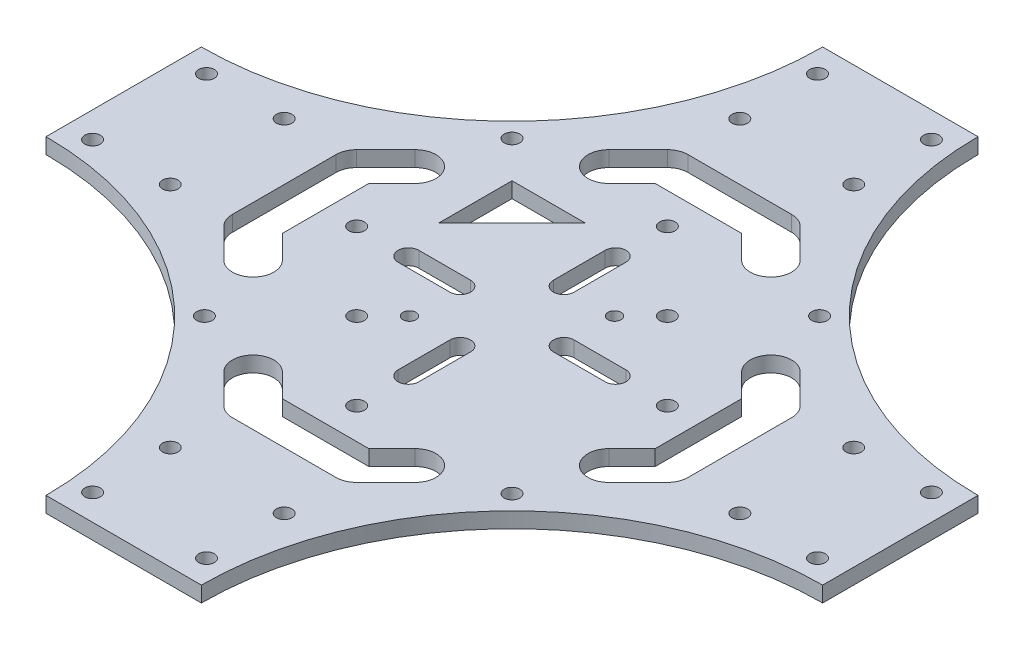
SolidWorks part; units mm, degrees
material "Hexcel AS4C (3000 丝)"
ref_plane "前视基准面" through (0, 0, 0) normal (0, 0, 1) x (1, 0, 0)
ref_plane "上视基准面" through (0, 0, 0) normal (0, 1, 0) x (1, 0, 0)
ref_plane "右视基准面" through (0, 0, 0) normal (1, 0, 0) x (0, 0, -1)
sketch "草图1" plane through (0, 0, 0) normal (0, 1, 0) x (1, 0, 0)
  line L0 (0, 0) -> (0, 75)
  line L1 (0, 0) -> (75, 0)
  line L2 (0, 0) -> (0, -75)
  line L3 (0, 0) -> (-75, 0)
  line L4 (0, 75) -> (15, 75)
  line L5 (0, 75) -> (-15, 75)
  line L6 (75, 0) -> (75, 15)
  line L7 (75, 0) -> (75, -15)
  line L8 (0, -75) -> (15, -75)
  line L9 (0, -75) -> (-15, -75)
  line L10 (-75, 0) -> (-75, -15)
  line L11 (-75, 0) -> (-75, 15)
  line L12 (75, 0) -> (70, 0)
  arc A0 (-75, 15) -> (-15, 75) centre (-75, 75) ccw
  arc A1 (15, 75) -> (75, 15) centre (75, 75) ccw
  arc A2 (75, -15) -> (15, -75) centre (75, -75) ccw
  arc A3 (-15, -75) -> (-75, -15) centre (-75, -75) ccw
  circle A4 centre (-11, 70) radius 1.25
  circle A5 centre (11, 70) radius 1.25
  circle A6 centre (70, -11) radius 1.25
  circle A7 centre (70, 11) radius 1.25
  circle A8 centre (-11, -70) radius 1.25
  circle A9 centre (11, -70) radius 1.25
  circle A10 centre (-70, 11) radius 1.25
  circle A11 centre (-70, -11) radius 1.25
  point P9 (0, 0)
  point P21 (0, 0)
  point P32 (0, 0)
  point P35 (0, 0)
  point P44 (0, 0)
  dimension "D1" = 4
extrude "凸台-拉伸1" add sketch "草图1" along normal blind 3 contours A2 L7 L1 L2 L8 A9 A6 | A3 L9 L2 L3 L10 A11 A8 | A0 L11 L3 L0 L5 A4 A10 | A1 L4 L0 L1 L6 A7 A5 region at (-25.2829, 0, -25.2829) region at (25.2829, 0, -25.2829) region at (25.2829, 0, 25.2829) region at (-25.2829, 0, 25.2829)
sketch "草图2" plane through (0, 0, 0) normal (0, -1, 0) x (1, 0, 0)
  line L0 (0, 0) -> (-32.5736, -32.5736)
  line L1 (0, 0) -> (32.5736, -32.5736)
  line L2 (-31.4663, 0.3536) -> (-0.3536, 31.4663)
  line L3 (31.4663, -0.3536) -> (-0.3536, 31.4663)
  line L4 (0.3536, -31.4663) -> (31.4663, -0.3536)
  line L5 (0.3536, -31.4663) -> (-31.4663, 0.3536)
  arc A0 (-15, -75) -> (-75, -15) centre (-75, -75) ccw construction
  circle A2 centre (0.3536, -31.4663) radius 1.5
  circle A3 centre (31.4663, -0.3536) radius 1.5
  circle A4 centre (-0.3536, 31.4663) radius 1.5
  circle A5 centre (-31.4663, 0.3536) radius 1.5
  point P12 (-15.5563, -15.5563)
  point P16 (-15.9099, 15.9099)
  point P17 (15.9099, -15.9099)
extrude "切除-拉伸1" cut sketch "草图2" against normal blind 3 contours A3 | A2 | A5 | A4
sketch "草图3" plane through (0, 3, 0) normal (0, 1, 0) x (1, 0, 0)
  line L0 (0.3536, 31.4663) -> (-31.4663, -0.3536)
  line L1 (-15.5563, 15.5563) -> (-22.6274, 22.6274)
  line L2 (-15.5563, 15.5563) -> (-12.0208, 19.0919)
  line L3 (-15.5563, 15.5563) -> (-19.0919, 12.0208)
  line L4 (-19.0919, 12.0208) -> (-22.6274, 22.6274)
  line L5 (-12.0208, 19.0919) -> (-22.6274, 22.6274)
extrude "切除-拉伸2" cut sketch "草图3" against normal blind 3 contours L0 L5 L1 | L4 L0 L1 region at (-16.7349, 3, -19.0919) region at (-19.0919, 3, -16.7349)
sketch "草图4" plane through (0, 3, 0) normal (0, 1, 0) x (1, 0, 0)
  line L0 (31.4663, 0.3536) -> (-0.3536, -31.4663)
  line L1 (0, 0) -> (21.2132, -21.2132)
  line L2 (28.2843, -14.1421) -> (14.1421, -28.2843)
  line L3 (14.1421, -28.2843) -> (28.2843, -14.1421) construction
  line L4 (8.4817, -22.6239) -> (22.6239, -8.4817)
  line L5 (19.8025, -33.9447) -> (33.9447, -19.8025)
  arc A0 (8.4817, -22.6239) -> (19.8025, -33.9447) centre (14.1421, -28.2843) ccw
  arc A1 (33.9447, -19.8025) -> (22.6239, -8.4817) centre (28.2843, -14.1421) ccw
  point P9 (21.2132, -21.2132)
extrude "切除-拉伸3" cut sketch "草图4" against normal blind 3 contours L5 A1 L0 A0 region at (21.2143, 3, 21.2143)
sketch "草图5" plane through (0, 3, 0) normal (0, 1, 0) x (1, 0, 0)
  line L0 (-12.0208, 19.0919) -> (-8.4853, 22.6274)
  line L1 (-8.4853, 22.6274) -> (-22.6274, 22.6274)
  line L2 (-19.0919, 12.0208) -> (-22.6274, 8.4853)
  line L3 (-22.6274, 8.4853) -> (-22.6274, 22.6274)
  line L4 (-12.0208, 19.0919) -> (-22.6274, 22.6274)
  line M28 (-19.0919, 12.0208) -> (-22.6274, 22.6274)
extrude "切除-拉伸4" cut sketch "草图5" against normal blind 10 contours L3 L2 M28 | L4 L0 L1 region at (-21.4489, 3, -14.3778)
sketch "草图6" plane through (0, 3, 0) normal (0, 1, 0) x (1, 0, 0)
  line L0 (0, 0) -> (-28.2843, -28.2843)
  line L1 (-28.2843, -28.2843) -> (-35.3553, -21.2132)
  line L2 (0, 0) -> (-22.6274, 22.6274)
  circle A0 centre (-35.3553, -21.2132) radius 1.5
  circle A1 centre (-21.2132, -35.3553) radius 1.5
  circle A2 centre (35.3553, 21.2132) radius 1.5
  circle A3 centre (21.2132, 35.3553) radius 1.5
extrude "切除-拉伸5" cut sketch "草图6" against normal blind 10 contours A1 | A0 | A2 | A3
sketch "草图7" plane through (0, 3, 0) normal (0, 1, 0) x (1, 0, 0)
  circle A0 centre (-29.6985, 29.6985) radius 1.5
  circle A1 centre (29.6985, 29.6985) radius 1.5
  circle A2 centre (29.6985, -29.6985) radius 1.5
  circle A3 centre (-29.6985, -29.6985) radius 1.5
  point P11 (0, 0)
  dimension "D1" = 4
extrude "切除-拉伸8" cut sketch "草图7" against normal blind 10
sketch "草图8" plane through (0, 3, 0) normal (0, 1, 0) x (1, 0, 0)
  circle A0 centre (-11, 55) radius 1.5
  circle A1 centre (11, 55) radius 1.5
  circle A2 centre (55, 11) radius 1.5
  circle A3 centre (55, -11) radius 1.5
  circle A4 centre (11, -55) radius 1.5
  circle A5 centre (-11, -55) radius 1.5
  circle A6 centre (-55, -11) radius 1.5
  circle A7 centre (-55, 11) radius 1.5
  point P21 (0, 0)
  dimension "D1" = 4
extrude "切除-拉伸9" cut sketch "草图8" against normal blind 10
sketch "草图9" plane through (0, 3, 0) normal (0, 1, 0) x (1, 0, 0)
  circle A0 centre (0, 0) radius 15
extrude "切除-拉伸10" cut sketch "草图9" against normal blind 10
sketch "草图11" plane through (0, 3, 0) normal (0, 1, 0) x (1, 0, 0)
  circle A0 centre (-35.3553, -21.2132) radius 1.5
  circle A2 centre (35.3553, 21.2132) radius 1.5
  circle A3 centre (21.2132, 35.3553) radius 1.5
  circle A4 centre (0.3536, 31.4663) radius 1.5
  circle A5 centre (31.4663, 0.3536) radius 1.5
  circle A6 centre (-0.3536, -31.4663) radius 1.5
  circle A7 centre (-31.4663, -0.3536) radius 1.5
  circle A8 centre (-21.2132, -35.3553) radius 1.5
extrude "凸台-拉伸3" add sketch "草图11" against normal blind 3
sketch "草图12" plane through (0, 3, 0) normal (0, 1, 0) x (1, 0, 0)
  line L0 (0, 0) -> (-40, 0)
  line L1 (-40, 0) -> (-40, 10)
  line L2 (-40, 0) -> (-40, -10)
  line L3 (-40, -10) -> (-40, 10) construction
  line L4 (-44, -10) -> (-44, 10)
  line L5 (-36, -10) -> (-36, 10)
  line L6 (-10, 40) -> (10, 40) construction
  line L7 (-10, 44) -> (10, 44)
  line L8 (-10, 36) -> (10, 36)
  line L9 (40, 10) -> (40, -10) construction
  line L10 (44, 10) -> (44, -10)
  line L11 (36, 10) -> (36, -10)
  line L12 (10, -40) -> (-10, -40) construction
  line L13 (10, -44) -> (-10, -44)
  line L14 (10, -36) -> (-10, -36)
  arc A0 (-44, -10) -> (-36, -10) centre (-40, -10) ccw
  arc A1 (-36, 10) -> (-44, 10) centre (-40, 10) ccw
  arc A2 (-10, 44) -> (-10, 36) centre (-10, 40) ccw
  arc A3 (10, 36) -> (10, 44) centre (10, 40) ccw
  arc A4 (44, 10) -> (36, 10) centre (40, 10) ccw
  arc A5 (36, -10) -> (44, -10) centre (40, -10) ccw
  arc A6 (10, -44) -> (10, -36) centre (10, -40) ccw
  arc A7 (-10, -36) -> (-10, -44) centre (-10, -40) ccw
  point P3 (-40, 0)
  point P13 (0, 40)
  point P20 (40, 0)
  point P27 (0, -40)
  point P34 (0, 0)
  dimension "D1" = 4
extrude "切除-拉伸12" cut sketch "草图12" against normal blind 3 contours L5 A1 L4 A0 | L8 A3 L7 A2 | L11 A5 L10 A4 | L14 A7 L13 A6 region at (-43.7088, 3, 0) region at (0, 3, -40) region at (40, 3, 0) region at (0, 3, 40)
sketch "草图14" plane through (0, 3, 0) normal (0, 1, 0) x (1, 0, 0)
  line L0 (22.8277, -8.285) -> (8.285, -22.8277) construction
  line L1 (19.8025, -33.9447) -> (33.9447, -19.8025) construction
  line L2 (8.285, -22.8277) -> (22.8277, -8.285)
  line L3 (22.8277, -8.285) -> (19.8025, -33.9447)
  line L4 (19.8025, -33.9447) -> (33.9447, -19.8025)
  arc A0 (8.285, -22.8277) -> (19.8025, -33.9447) centre (14.1421, -28.2843) ccw
  arc A1 (8.285, -22.8277) -> (19.8025, -33.9447) centre (14.1421, -28.2843) ccw construction
  arc A2 (33.9447, -19.8025) -> (22.8277, -8.285) centre (28.2843, -14.1421) ccw construction
  arc A3 (22.8277, -8.285) -> (32.1857, -7.1522) centre (28.2843, -14.1421) ccw
  circle A4 centre (28.2843, -14.1421) radius 8.005
extrude "凸台-拉伸4" add sketch "草图14" against normal blind 3 contours A3 A4 L3 | L2 A3 L3 | A3 L2 A0 L3 | A3 L3 L4 region at (14.6624, 3, 25.7239) region at (21.4582, 3, 13.3381) region at (24.21, 3, 25.4431) region at (28.7736, 3, 14.1998)
sketch "草图15" plane through (0, 3, 0) normal (0, 1, 0) x (1, 0, 0)
  circle A0 centre (0, 0) radius 15
extrude "凸台-拉伸5" add sketch "草图15" against normal blind 3
sketch "草图17" plane through (0, 3, 0) normal (0, 1, 0) x (1, 0, 0)
  line L0 (0, 0) -> (0, -20)
  line L1 (0, -20) -> (0, -10) construction
  line L2 (-2, -20) -> (-2, -10)
  line L3 (2, -20) -> (2, -10)
  line L4 (-20, 0) -> (-10, 0) construction
  line L5 (-20, 2) -> (-10, 2)
  line L6 (-20, -2) -> (-10, -2)
  line L7 (0, 20) -> (0, 10) construction
  line L8 (2, 20) -> (2, 10)
  line L9 (-2, 20) -> (-2, 10)
  line L10 (20, 0) -> (10, 0) construction
  line L11 (20, -2) -> (10, -2)
  line L12 (20, 2) -> (10, 2)
  arc A0 (-2, -20) -> (2, -20) centre (0, -20) ccw
  arc A1 (2, -10) -> (-2, -10) centre (0, -10) ccw
  arc A2 (-20, 2) -> (-20, -2) centre (-20, 0) ccw
  arc A3 (-10, -2) -> (-10, 2) centre (-10, 0) ccw
  arc A4 (2, 20) -> (-2, 20) centre (0, 20) ccw
  arc A5 (-2, 10) -> (2, 10) centre (0, 10) ccw
  arc A6 (20, -2) -> (20, 2) centre (20, 0) ccw
  arc A7 (10, 2) -> (10, -2) centre (10, 0) ccw
  point P3 (0, -15)
  point P13 (-15, 0)
  point P20 (0, 15)
  point P27 (15, 0)
  point P33 (0, 0)
  dimension "D1" = 4
extrude "切除-拉伸13" cut sketch "草图17" against normal blind 3 contours L8 A5 L9 A4 | L12 A7 L11 A6 | L3 A1 L2 A0 | L5 A3 L6 A2
sketch "草图18" plane through (0, 3, 0) normal (0, 1, 0) x (1, 0, 0)
  line L0 (0, 0) -> (-32.5736, 32.5736)
  line L1 (-32.5736, 32.5736) -> (-46.7157, 46.7157)
  line L2 (-50.2513, 50.2513) -> (-61.9773, 38.5252)
  line L3 (-46.7157, 46.7157) -> (-50.2513, 50.2513)
  line L4 (-61.9773, 38.5252) -> (-38.5252, 61.9773)
  line L5 (-38.5252, 61.9773) -> (-22.5002, 45.9523)
  line L6 (-61.9773, 38.5252) -> (-45.9523, 22.5002)
  arc A0 (-75, 15) -> (-15, 75) centre (-75, 75) ccw construction
  circle A1 centre (-67.9289, 67.9289) radius 30
  circle A2 centre (-75, 75) radius 60
extrude "凸台-拉伸7" add sketch "草图18" against normal blind 3 contours L4 A1 L2 | L2 A1 L3 | L3 A1 L4 | L6 A2 L1 A1 | L1 A2 L5 A1 region at (-46.4984, 3, -34.5306) region at (-34.5306, 3, -46.4984) region at (-53.277, 3, -44.3758) region at (-44.3758, 3, -53.277) region at (-68.7208, 3, -68.7208)
sketch "草图19" plane through (0, 3, 0) normal (0, 1, 0) x (1, 0, 0)
  line L0 (-61.9773, 38.5252) -> (-38.5252, 61.9773)
  line L1 (-50.2513, 50.2513) -> (-36.1091, 36.1091)
  line L2 (-36.1091, 36.1091) -> (-43.1802, 29.0381)
  line L3 (-36.1091, 36.1091) -> (-29.0381, 43.1802)
  line L4 (-29.0381, 43.1802) -> (-37.1408, 51.2829)
  line L5 (-37.1408, 51.2829) -> (-51.2829, 37.1408)
  line L6 (-51.2829, 37.1408) -> (-43.1802, 29.0381)
  circle A1 centre (-67.9289, 67.9289) radius 35
  circle A2 centre (-67.9289, 67.9289) radius 45
extrude "切除-拉伸14" cut sketch "草图19" against normal blind 3 contours L1 A2 L4 A1 | L6 A2 L1 A1 region at (-36.3949, 3, -43.5045) region at (-43.5045, 3, -36.3949)
sketch "草图21" plane through (0, 3, 0) normal (0, 1, 0) x (1, 0, 0)
  line L0 (-61.9773, 38.5252) -> (-38.5252, 61.9773)
  line L1 (-67.9289, 67.9289) -> (-53.7868, 53.7868)
  line L2 (-82.0711, 82.0711) -> (-75, 75)
  line L3 (-67.9289, 67.9289) -> (-82.0711, 82.0711)
  line L4 (-53.7868, 53.7868) -> (-60.8579, 60.8579)
  line L5 (-82.0711, 82.0711) -> (-75, 75) construction
  line L6 (-81.1872, 82.955) -> (-74.1161, 75.8839)
  line L7 (-82.955, 81.1872) -> (-75.8839, 74.1161)
  line L8 (-60.8579, 60.8579) -> (-53.7868, 53.7868) construction
  line L9 (-59.974, 61.7417) -> (-52.9029, 54.6707)
  line L10 (-61.7417, 59.974) -> (-54.6707, 52.9029)
  arc A0 (-81.1872, 82.955) -> (-82.955, 81.1872) centre (-82.0711, 82.0711) ccw
  arc A1 (-75.8839, 74.1161) -> (-74.1161, 75.8839) centre (-75, 75) ccw
  arc A2 (-59.974, 61.7417) -> (-61.7417, 59.974) centre (-60.8579, 60.8579) ccw
  arc A3 (-54.6707, 52.9029) -> (-52.9029, 54.6707) centre (-53.7868, 53.7868) ccw
  point P2 (-78.5355, 78.5355)
  point P15 (-57.3223, 57.3223)
extrude "切除-拉伸15" cut sketch "草图21" against normal blind 3 contours A1 L6 A0 L7 | A3 L9 A2 L10 region at (-75, 3, -73.8854)
pattern_circular "阵列(圆周)1" count 8 over 360 about axis through (-67.9289, 3, -67.9289) along (0, 1, 0) of "切除-拉伸15"
sketch "草图22" plane through (0, 3, 0) normal (0, 1, 0) x (1, 0, 0)
  line L0 (0, 0) -> (9.8995, 9.8995)
  line L1 (0, 0) -> (-9.8995, -9.8995)
  circle A0 centre (9.8995, 9.8995) radius 1.25
  circle A1 centre (-9.8995, -9.8995) radius 1.25
extrude "切除-拉伸17" cut sketch "草图22" against normal blind 3 contours A0 | A1
sketch "草图23" plane through (0, 3, 0) normal (0, 1, 0) x (1, 0, 0)
  circle A0 centre (0, 30) radius 1.5
  circle A1 centre (30, 0) radius 1.5
  circle A2 centre (0, -30) radius 1.5
  circle A3 centre (-30, 0) radius 1.5
  point P13 (0, 0)
  dimension "D1" = 4
extrude "切除-拉伸18" cut sketch "草图23" against normal blind 10
sketch "草图24" plane through (0, 3, 0) normal (0, 1, 0) x (1, 0, 0)
  circle A0 centre (-15, -15) radius 1.5
  circle A1 centre (15, 15) radius 1.5
extrude "切除-拉伸19" cut sketch "草图24" against normal blind 10
sketch "草图25" plane through (0, 3, 0) normal (0, 1, 0) x (1, 0, 0)
  circle A0 centre (-75, 75) radius 60
extrude "切除-拉伸20" cut sketch "草图25" against normal blind 10
sketch "草图26" plane through (0, 3, 0) normal (0, 1, 0) x (1, 0, 0)
  line L0 (-15, 75) -> (-75, 15)
  circle A0 centre (-75, 75) radius 60
extrude "凸台-拉伸8" add sketch "草图26" against normal blind 3 contours L0 A0 region at (-39.9612, 3, -39.9612)
sketch "草图27" plane through (0, 0, 0) normal (0, -1, 0) x (1, 0, 0)
  line L0 (-45, -45) -> (-23.5998, -66.4002)
  line L1 (-15, -75) -> (-75, -15) construction
  line L2 (-23.5998, -66.4002) -> (-66.0262, -23.9738)
  line L3 (-15, -75) -> (-22.0711, -82.0711)
  line L4 (-22.0711, -82.0711) -> (-75, -15)
  line L5 (-75, -15) -> (-82.0711, -22.0711)
  line L6 (-82.0711, -22.0711) -> (-22.0711, -82.0711)
  line L7 (75, 15) -> (15, 75)
  line L8 (15, 75) -> (22.0711, 82.0711)
  line L9 (75, 15) -> (82.0711, 22.0711)
  line L10 (82.0711, 22.0711) -> (22.0711, 82.0711)
  line L11 (-15, -75) -> (-75, -15)
  line L12 (-22.0711, -82.0711) -> (-29.1421, -89.1421)
  line L13 (-29.1421, -89.1421) -> (-82.0711, -22.0711)
  line L14 (-82.0711, -22.0711) -> (-89.1421, -29.1421)
  line L15 (-89.1421, -29.1421) -> (-29.1421, -89.1421)
  circle A0 centre (75, 75) radius 60
extrude "凸台-拉伸10" add sketch "草图27" against normal blind 3 contours L14 L15 L13 | L13 L12 L6 | L5 L6 L4 | L3 L11 L0 L2 L4 region at (-37.357, 0, -57.357) region at (-59.714, 0, -39.714) region at (-44.4281, 0, -64.4281) region at (-66.7851, 0, -46.7851)
sketch "草图28" plane through (0, 0, 0) normal (0, -1, 0) x (1, 0, 0)
  line L0 (-59.1421, -59.1421) -> (-52.0711, -52.0711)
  line L1 (-89.1421, -29.1421) -> (-29.1421, -89.1421) construction
  line L2 (-52.0711, -52.0711) -> (-25.9081, -78.234)
  line L3 (-52.0711, -52.0711) -> (-78.234, -25.9081)
  line L4 (11, -70) -> (8.198, -68.4493)
  circle A1 centre (11, -70) radius 1.5
  circle A2 centre (-11, -70) radius 1.5
  circle A3 centre (-70, -11) radius 1.5
  circle A4 centre (-70, 11) radius 1.5
  circle A5 centre (-11, 70) radius 1.5
  circle A6 centre (11, 70) radius 1.5
  circle A7 centre (70, 11) radius 1.5
  circle A8 centre (70, -11) radius 1.5
  circle A9 centre (-25.9081, -78.234) radius 1.54
  circle A10 centre (-78.234, -25.9081) radius 1.52
extrude "切除-拉伸21" cut sketch "草图28" against normal blind 3 contours A9 | A10 | A3 | A4 | A2 | A1 | A8 | A7 | A5 | A6 region at (-25.3355, 0, -76.8515) region at (-79.5986, 0, -25.3429)
sketch "草图29" plane through (0, 0, 0) normal (0, -1, 0) x (1, 0, 0)
  line L0 (-59.1421, -59.1421) -> (-22.6274, -22.6274)
  line L1 (-78.234, -25.9081) -> (-68.3345, -35.8076)
  line L2 (-89.1421, -29.1421) -> (-29.1421, -89.1421) construction
  circle A0 centre (-68.3345, -35.8076) radius 1.5
  circle A1 centre (-35.8076, -68.3345) radius 1.5
extrude "切除-拉伸22" cut sketch "草图29" against normal blind 3 contours A1 | A0
sketch "草图30" plane through (0, 0, 0) normal (0, -1, 0) x (1, 0, 0)
  line L0 (-29.1421, -89.1421) -> (-89.1421, -29.1421)
  line L1 (-29.1421, -89.1421) -> (-43.2843, -103.2843)
  line L2 (-89.1421, -29.1421) -> (-103.2843, -43.2843)
  line L3 (-43.2843, -103.2843) -> (-103.2843, -43.2843)
extrude "凸台-拉伸11" add sketch "草图30" against normal blind 3
sketch "草图31" plane through (0, 0, 0) normal (0, -1, 0) x (1, 0, 0)
  line L1 (-25.9081, -78.234) -> (-78.234, -25.9081)
  circle A0 centre (-43.5858, -95.9117) radius 1.5
  circle A1 centre (-53.4853, -86.0122) radius 1.5
  circle A2 centre (-86.0122, -53.4853) radius 1.5
  circle A3 centre (-95.9117, -43.5858) radius 1.5
extrude "切除-拉伸23" cut sketch "草图31" against normal blind 3 contours A0 | A1 | A2 | A3
sketch "草图32" plane through (0, 0, 0) normal (0, -1, 0) x (1, 0, 0)
  line L0 (75, 15) -> (15, 75)
  line L1 (75, 15) -> (15, 75)
  line L2 (75, 15) -> (89.1421, 29.1421)
  line L3 (15, 75) -> (29.1421, 89.1421)
  line L4 (89.1421, 29.1421) -> (29.1421, 89.1421)
  circle A0 centre (75, 75) radius 60
extrude "凸台-拉伸12" add sketch "草图32" against normal blind 3 contours L0 A0 | L2 L4 L3 L0 region at (39.9612, 0, 39.9612) region at (52.0711, 0, 52.0711)
sketch "草图33" plane through (0, 0, 0) normal (0, -1, 0) x (-1, 0, 0)
  line L0 (-29.6985, -29.6985) -> (-59.1421, -59.1421)
  line L1 (-89.1421, -29.1421) -> (-29.1421, -89.1421) construction
  line L2 (-44.4203, -44.4203) -> (-14.6894, -44.4203)
  line L3 (-14.6894, -44.4203) -> (-44.4203, -16.8394)
  line L4 (-44.4203, -16.8394) -> (-44.4203, -44.4203)
  line L5 (-29.5549, -44.4203) -> (-19.5549, -44.4203) construction
  line L6 (-29.5549, -42.92) -> (-19.5549, -42.92)
  line L7 (-29.5549, -45.9207) -> (-19.5549, -45.9207)
  line L8 (-44.4203, -59.2858) -> (-44.4203, -69.2858) construction
  line L9 (-42.92, -59.2858) -> (-42.92, -69.2858)
  line L10 (-45.9207, -59.2858) -> (-45.9207, -69.2858)
  line L11 (-59.2858, -44.4203) -> (-69.2858, -44.4203) construction
  line L12 (-59.2858, -45.9207) -> (-69.2858, -45.9207)
  line L13 (-59.2858, -42.92) -> (-69.2858, -42.92)
  line L14 (-44.4203, -29.5549) -> (-44.4203, -19.5549) construction
  line L15 (-45.9207, -29.5549) -> (-45.9207, -19.5549)
  line L16 (-42.92, -29.5549) -> (-42.92, -19.5549)
  arc A0 (-29.5549, -42.92) -> (-29.5549, -45.9207) centre (-29.5549, -44.4203) ccw
  arc A1 (-19.5549, -45.9207) -> (-19.5549, -42.92) centre (-19.5549, -44.4203) ccw
  arc A2 (-42.92, -59.2858) -> (-45.9207, -59.2858) centre (-44.4203, -59.2858) ccw
  arc A3 (-45.9207, -69.2858) -> (-42.92, -69.2858) centre (-44.4203, -69.2858) ccw
  arc A4 (-59.2858, -45.9207) -> (-59.2858, -42.92) centre (-59.2858, -44.4203) ccw
  arc A5 (-69.2858, -42.92) -> (-69.2858, -45.9207) centre (-69.2858, -44.4203) ccw
  arc A6 (-45.9207, -29.5549) -> (-42.92, -29.5549) centre (-44.4203, -29.5549) ccw
  arc A7 (-42.92, -19.5549) -> (-45.9207, -19.5549) centre (-44.4203, -19.5549) ccw
  point P10 (-24.5549, -44.4203)
  point P20 (-44.4203, -64.2858)
  point P27 (-64.2858, -44.4203)
  point P34 (-44.4203, -24.5549)
  point P39 (-44.4203, -44.4203)
  dimension "D1" = 4
extrude "切除-拉伸24" cut sketch "草图33" against normal blind 3 contours L10 A3 L9 A2 | L7 A1 L6 A0 | L12 A5 L13 A4 | L15 A7 L16 A6
sketch "草图34" plane through (0, 0, 0) normal (0, -1, 0) x (1, 0, 0)
  line L0 (29.1421, 89.1421) -> (89.1421, 29.1421)
  line L1 (29.1421, 89.1421) -> (43.2843, 103.2843)
  line L2 (89.1421, 29.1421) -> (103.2843, 43.2843)
  line L3 (43.2843, 103.2843) -> (103.2843, 43.2843)
  line L4 (75, 15) -> (89.1421, 29.1421) construction
  line L5 (89.1421, 29.1421) -> (29.1421, 89.1421) construction
extrude "凸台-拉伸13" add sketch "草图34" against normal blind 3
sketch "草图35" plane through (0, 0, 0) normal (0, -1, 0) x (1, 0, 0)
  line L0 (10, 40) -> (15.6569, 34.3431)
  line L1 (10, 40) -> (15.6569, 34.3431) construction
  line L2 (12.8284, 42.8284) -> (18.4853, 37.1716)
  line L3 (7.1716, 37.1716) -> (12.8284, 31.5147)
  line L4 (-10, 40) -> (-15.6569, 34.3431) construction
  line L5 (-7.1716, 37.1716) -> (-12.8284, 31.5147)
  line L6 (-12.8284, 42.8284) -> (-18.4853, 37.1716)
  line L7 (40, -10) -> (34.3431, -15.6569) construction
  line L8 (42.8284, -12.8284) -> (37.1716, -18.4853)
  line L9 (37.1716, -7.1716) -> (31.5147, -12.8284)
  line L10 (40, 10) -> (34.3431, 15.6569) construction
  line L11 (37.1716, 7.1716) -> (31.5147, 12.8284)
  line L12 (42.8284, 12.8284) -> (37.1716, 18.4853)
  line L13 (-10, -40) -> (-15.6569, -34.3431) construction
  line L14 (-12.8284, -42.8284) -> (-18.4853, -37.1716)
  line L15 (-7.1716, -37.1716) -> (-12.8284, -31.5147)
  line L16 (10, -40) -> (15.6569, -34.3431) construction
  line L17 (7.1716, -37.1716) -> (12.8284, -31.5147)
  line L18 (12.8284, -42.8284) -> (18.4853, -37.1716)
  line L19 (-40, 10) -> (-34.3431, 15.6569) construction
  line L20 (-42.8284, 12.8284) -> (-37.1716, 18.4853)
  line L21 (-37.1716, 7.1716) -> (-31.5147, 12.8284)
  line L22 (-40, -10) -> (-34.3431, -15.6569) construction
  line L23 (-37.1716, -7.1716) -> (-31.5147, -12.8284)
  line L24 (-42.8284, -12.8284) -> (-37.1716, -18.4853)
  arc A0 (12.8284, 42.8284) -> (7.1716, 37.1716) centre (10, 40) ccw
  arc A1 (12.8284, 31.5147) -> (18.4853, 37.1716) centre (15.6569, 34.3431) ccw
  arc A2 (-7.1716, 37.1716) -> (-12.8284, 42.8284) centre (-10, 40) ccw
  arc A3 (-18.4853, 37.1716) -> (-12.8284, 31.5147) centre (-15.6569, 34.3431) ccw
  arc A4 (42.8284, -12.8284) -> (37.1716, -7.1716) centre (40, -10) ccw
  arc A5 (31.5147, -12.8284) -> (37.1716, -18.4853) centre (34.3431, -15.6569) ccw
  arc A6 (37.1716, 7.1716) -> (42.8284, 12.8284) centre (40, 10) ccw
  arc A7 (37.1716, 18.4853) -> (31.5147, 12.8284) centre (34.3431, 15.6569) ccw
  arc A8 (-12.8284, -42.8284) -> (-7.1716, -37.1716) centre (-10, -40) ccw
  arc A9 (-12.8284, -31.5147) -> (-18.4853, -37.1716) centre (-15.6569, -34.3431) ccw
  arc A10 (7.1716, -37.1716) -> (12.8284, -42.8284) centre (10, -40) ccw
  arc A11 (18.4853, -37.1716) -> (12.8284, -31.5147) centre (15.6569, -34.3431) ccw
  arc A12 (-42.8284, 12.8284) -> (-37.1716, 7.1716) centre (-40, 10) ccw
  arc A13 (-31.5147, 12.8284) -> (-37.1716, 18.4853) centre (-34.3431, 15.6569) ccw
  arc A14 (-37.1716, -7.1716) -> (-42.8284, -12.8284) centre (-40, -10) ccw
  arc A15 (-37.1716, -18.4853) -> (-31.5147, -12.8284) centre (-34.3431, -15.6569) ccw
  point P3 (12.8284, 37.1716)
  point P11 (-12.8284, 37.1716)
  point P21 (37.1716, -12.8284)
  point P28 (37.1716, 12.8284)
  point P35 (-12.8284, -37.1716)
  point P42 (12.8284, -37.1716)
  point P49 (-37.1716, 12.8284)
  point P56 (-37.1716, -12.8284)
  point P61 (0, 0)
  dimension "D1" = 4
extrude "切除-拉伸25" cut sketch "草图35" against normal blind 10 contours L12 A7 L11 A6 | L3 A1 L2 A0 | L6 A3 L5 A2 | L21 A13 L20 A12 | L24 A15 L23 A14 | L15 A9 L14 A8 | L18 A11 L17 A10 | L9 A5 L8 A4 region at (15.5203, 0, 39.8634) region at (-12.8284, 0, 37.1716) region at (37.1716, 0, -12.8284) region at (37.1716, 0, 12.8284) region at (-12.8284, 0, -37.1716) region at (12.8284, 0, -37.1716) region at (-37.1716, 0, 12.8284) region at (-37.1716, 0, -12.8284)
sketch "草图36" plane through (0, 0, 0) normal (0, -1, 0) x (1, 0, 0)
  line L0 (19.5549, 44.4203) -> (29.5549, 44.4203) construction
  line L1 (19.5549, 45.9203) -> (29.5549, 45.9203)
  line L2 (19.5549, 42.9203) -> (29.5549, 42.9203)
  line L3 (26.6259, 51.4914) -> (36.6259, 51.4914) construction
  line L4 (44.4203, 69.2858) -> (44.4203, 59.2858) construction
  line L5 (45.9203, 69.2858) -> (45.9203, 59.2858)
  line L6 (42.9203, 69.2858) -> (42.9203, 59.2858)
  line L7 (69.2858, 44.4203) -> (59.2858, 44.4203) construction
  line L8 (69.2858, 42.9203) -> (59.2858, 42.9203)
  line L9 (69.2858, 45.9203) -> (59.2858, 45.9203)
  line L10 (44.4203, 19.5549) -> (44.4203, 29.5549) construction
  line L11 (42.9203, 19.5549) -> (42.9203, 29.5549)
  line L12 (45.9203, 19.5549) -> (45.9203, 29.5549)
  line L13 (26.6259, 52.9914) -> (36.6259, 52.9914)
  line L14 (26.6259, 49.9914) -> (36.6259, 49.9914)
  line L15 (51.4914, 76.3568) -> (51.4914, 66.3568) construction
  line L16 (52.9914, 76.3568) -> (52.9914, 66.3568)
  line L17 (49.9914, 76.3568) -> (49.9914, 66.3568)
  line L18 (76.3568, 51.4914) -> (66.3568, 51.4914) construction
  line L19 (76.3568, 49.9914) -> (66.3568, 49.9914)
  line L20 (76.3568, 52.9914) -> (66.3568, 52.9914)
  line L21 (51.4914, 26.6259) -> (51.4914, 36.6259) construction
  line L22 (49.9914, 26.6259) -> (49.9914, 36.6259)
  line L23 (52.9914, 26.6259) -> (52.9914, 36.6259)
  arc A0 (19.5549, 45.9203) -> (19.5549, 42.9203) centre (19.5549, 44.4203) ccw
  arc A1 (29.5549, 42.9203) -> (29.5549, 45.9203) centre (29.5549, 44.4203) ccw
  arc A2 (45.9203, 69.2858) -> (42.9203, 69.2858) centre (44.4203, 69.2858) ccw
  arc A3 (42.9203, 59.2858) -> (45.9203, 59.2858) centre (44.4203, 59.2858) ccw
  arc A4 (69.2858, 42.9203) -> (69.2858, 45.9203) centre (69.2858, 44.4203) ccw
  arc A5 (59.2858, 45.9203) -> (59.2858, 42.9203) centre (59.2858, 44.4203) ccw
  arc A6 (42.9203, 19.5549) -> (45.9203, 19.5549) centre (44.4203, 19.5549) ccw
  arc A7 (45.9203, 29.5549) -> (42.9203, 29.5549) centre (44.4203, 29.5549) ccw
  arc A8 (26.6259, 52.9914) -> (26.6259, 49.9914) centre (26.6259, 51.4914) ccw
  arc A9 (36.6259, 49.9914) -> (36.6259, 52.9914) centre (36.6259, 51.4914) ccw
  arc A10 (52.9914, 76.3568) -> (49.9914, 76.3568) centre (51.4914, 76.3568) ccw
  arc A11 (49.9914, 66.3568) -> (52.9914, 66.3568) centre (51.4914, 66.3568) ccw
  arc A12 (76.3568, 49.9914) -> (76.3568, 52.9914) centre (76.3568, 51.4914) ccw
  arc A13 (66.3568, 52.9914) -> (66.3568, 49.9914) centre (66.3568, 51.4914) ccw
  arc A14 (49.9914, 26.6259) -> (52.9914, 26.6259) centre (51.4914, 26.6259) ccw
  arc A15 (52.9914, 36.6259) -> (49.9914, 36.6259) centre (51.4914, 36.6259) ccw
  point P4 (24.5549, 44.4203)
  point P13 (31.6259, 51.4914)
  point P19 (44.4203, 64.2858)
  point P26 (64.2858, 44.4203)
  point P33 (44.4203, 24.5549)
  point P41 (51.4914, 71.3568)
  point P48 (71.3568, 51.4914)
  point P55 (51.4914, 31.6259)
  dimension "D1" = 2
extrude "切除-拉伸26" cut sketch "草图36" against normal blind 10
sketch "草图37" plane through (0, 0, 0) normal (0, -1, 0) x (1, 0, 0)
  line L0 (44.4203, 69.2858) -> (44.4203, 59.8535) construction
  line L1 (47.888, 69.2858) -> (47.888, 59.8535)
  line L2 (40.9527, 69.2858) -> (40.9527, 59.8535)
  line L3 (60.035, 44.7696) -> (68.5031, 44.7696) construction
  line L4 (60.035, 48.1814) -> (68.5031, 48.1814)
  line L5 (60.035, 41.3579) -> (68.5031, 41.3579)
  line L6 (44.4203, 29.5549) -> (44.4203, 19.6289) construction
  line L7 (48.5122, 29.5549) -> (48.5122, 19.6289)
  line L8 (40.3284, 29.5549) -> (40.3284, 19.6289)
  line L9 (20.3241, 44.7696) -> (29.5195, 44.7696) construction
  line L10 (20.3241, 48.0853) -> (29.5195, 48.0853)
  line L11 (20.3241, 41.454) -> (29.5195, 41.454)
  arc A0 (47.888, 69.2858) -> (40.9527, 69.2858) centre (44.4203, 69.2858) ccw
  arc A1 (40.9527, 59.8535) -> (47.888, 59.8535) centre (44.4203, 59.8535) ccw
  arc A2 (60.035, 48.1814) -> (60.035, 41.3579) centre (60.035, 44.7696) ccw
  arc A3 (68.5031, 41.3579) -> (68.5031, 48.1814) centre (68.5031, 44.7696) ccw
  arc A4 (48.5122, 29.5549) -> (40.3284, 29.5549) centre (44.4203, 29.5549) ccw
  arc A5 (40.3284, 19.6289) -> (48.5122, 19.6289) centre (44.4203, 19.6289) ccw
  arc A6 (20.3241, 48.0853) -> (20.3241, 41.454) centre (20.3241, 44.7696) ccw
  arc A7 (29.5195, 41.454) -> (29.5195, 48.0853) centre (29.5195, 44.7696) ccw
  point P3 (44.4203, 64.5696)
  point P8 (64.2691, 44.7696)
  point P15 (44.4203, 24.5919)
  point P23 (24.9218, 44.7696)
extrude "凸台-拉伸14" add sketch "草图37" against normal blind 3
sketch "草图38" plane through (0, 0, 0) normal (0, -1, 0) x (1, 0, 0)
  line L0 (-52.4533, -52.4533) -> (-53.8675, -51.0391)
  line L1 (-51.0391, -53.8675) -> (-52.4533, -52.4533)
  line L2 (57.1482, 57.1482) -> (55.734, 58.5624)
  line L3 (-53.8675, -51.0391) -> (-51.0391, -51.0391)
  line L4 (-51.0391, -53.8675) -> (-51.0391, -51.0391)
  line L5 (58.5624, 55.734) -> (57.1482, 57.1482)
  line L6 (55.734, 58.5624) -> (58.5624, 58.5624)
  line L7 (58.5624, 55.734) -> (58.5624, 58.5624)
  line L8 (59.4914, 53.4914) -> (61.4914, 51.4914)
  line L9 (59.4914, 49.4914) -> (61.4914, 51.4914)
  line L10 (59.4914, 49.4914) -> (59.4914, 51.4914)
  line L11 (59.4914, 51.4914) -> (59.4914, 53.4914)
  line L12 (58.5624, 47.2487) -> (58.5624, 44.4203)
  line L13 (55.734, 44.4203) -> (58.5624, 44.4203)
  line L14 (55.734, 44.4203) -> (57.1482, 45.8345)
  line L15 (57.1482, 45.8345) -> (58.5624, 47.2487)
  line L16 (53.4914, 43.4914) -> (51.4914, 41.4914)
  line L17 (49.4914, 43.4914) -> (51.4914, 41.4914)
  line L18 (49.4914, 43.4914) -> (51.4914, 43.4914)
  line L19 (51.4914, 43.4914) -> (53.4914, 43.4914)
  line L20 (47.2487, 44.4203) -> (44.4203, 44.4203)
  line L21 (44.4203, 47.2487) -> (44.4203, 44.4203)
  line L22 (44.4203, 47.2487) -> (45.8345, 45.8345)
  line L23 (45.8345, 45.8345) -> (47.2487, 44.4203)
  line L24 (43.4914, 49.4914) -> (41.4914, 51.4914)
  line L25 (43.4914, 53.4914) -> (41.4914, 51.4914)
  line L26 (43.4914, 53.4914) -> (43.4914, 51.4914)
  line L27 (43.4914, 51.4914) -> (43.4914, 49.4914)
  line L28 (44.4203, 55.734) -> (44.4203, 58.5624)
  line L29 (47.2487, 58.5624) -> (44.4203, 58.5624)
  line L30 (47.2487, 58.5624) -> (45.8345, 57.1482)
  line L31 (45.8345, 57.1482) -> (44.4203, 55.734)
  line L32 (49.4914, 59.4914) -> (51.4914, 61.4914)
  line L33 (53.4914, 59.4914) -> (51.4914, 61.4914)
  line L34 (53.4914, 59.4914) -> (51.4914, 59.4914)
  line L35 (51.4914, 59.4914) -> (49.4914, 59.4914)
  line L36 (-50.1102, -56.1102) -> (-48.1102, -58.1102)
  line L37 (-50.1102, -60.1102) -> (-48.1102, -58.1102)
  line L38 (-50.1102, -60.1102) -> (-50.1102, -58.1102)
  line L39 (-50.1102, -58.1102) -> (-50.1102, -56.1102)
  line L40 (-51.0391, -62.3528) -> (-51.0391, -65.1812)
  line L41 (-53.8675, -65.1812) -> (-51.0391, -65.1812)
  line L42 (-53.8675, -65.1812) -> (-52.4533, -63.767)
  line L43 (-52.4533, -63.767) -> (-51.0391, -62.3528)
  line L44 (-56.1102, -66.1102) -> (-58.1102, -68.1102)
  line L45 (-60.1102, -66.1102) -> (-58.1102, -68.1102)
  line L46 (-60.1102, -66.1102) -> (-58.1102, -66.1102)
  line L47 (-58.1102, -66.1102) -> (-56.1102, -66.1102)
  line L48 (-62.3528, -65.1812) -> (-65.1812, -65.1812)
  line L49 (-65.1812, -62.3528) -> (-65.1812, -65.1812)
  line L50 (-65.1812, -62.3528) -> (-63.767, -63.767)
  line L51 (-63.767, -63.767) -> (-62.3528, -65.1812)
  line L52 (-66.1102, -60.1102) -> (-68.1102, -58.1102)
  line L53 (-66.1102, -56.1102) -> (-68.1102, -58.1102)
  line L54 (-66.1102, -56.1102) -> (-66.1102, -58.1102)
  line L55 (-66.1102, -58.1102) -> (-66.1102, -60.1102)
  line L56 (-65.1812, -53.8675) -> (-65.1812, -51.0391)
  line L57 (-62.3528, -51.0391) -> (-65.1812, -51.0391)
  line L58 (-62.3528, -51.0391) -> (-63.767, -52.4533)
  line L59 (-63.767, -52.4533) -> (-65.1812, -53.8675)
  line L60 (-60.1102, -50.1102) -> (-58.1102, -48.1102)
  line L61 (-56.1102, -50.1102) -> (-58.1102, -48.1102)
  line L62 (-56.1102, -50.1102) -> (-58.1102, -50.1102)
  line L63 (-58.1102, -50.1102) -> (-60.1102, -50.1102)
  circle A0 centre (51.4914, 51.4914) radius 6
  circle A1 centre (-58.1102, -58.1102) radius 6
  point P40 (51.4914, 51.4914)
  point P70 (-58.1102, -58.1102)
  dimension "D1" = 2
extrude "切除-拉伸28" cut sketch "草图38" against normal blind 3
sketch "草图39" plane through (0, 0, 0) normal (0, -1, 0) x (1, 0, 0)
  circle A0 centre (-69.7487, -69.7487) radius 1.5
  circle A1 centre (-73.9914, -65.5061) radius 1.5
  circle A2 centre (-78.234, -61.2635) radius 1.5
  circle A3 centre (-82.4767, -57.0208) radius 1.5
  circle A4 centre (-65.5061, -73.9914) radius 1.5
  circle A5 centre (-61.2635, -78.234) radius 1.5
  circle A6 centre (-57.0208, -82.4767) radius 1.5
extrude "切除-拉伸29" cut sketch "草图39" against normal blind 3
sketch "草图40" plane through (0, 0, 0) normal (0, -1, 0) x (1, 0, 0)
  circle A0 centre (75, -75) radius 60
  circle A1 centre (-75, -75) radius 60
  circle A2 centre (-75, 75) radius 60
  circle A3 centre (75, 75) radius 60
  point P12 (0, 0)
  dimension "D1" = 4
extrude "切除-拉伸30" cut sketch "草图40" against normal blind 10
